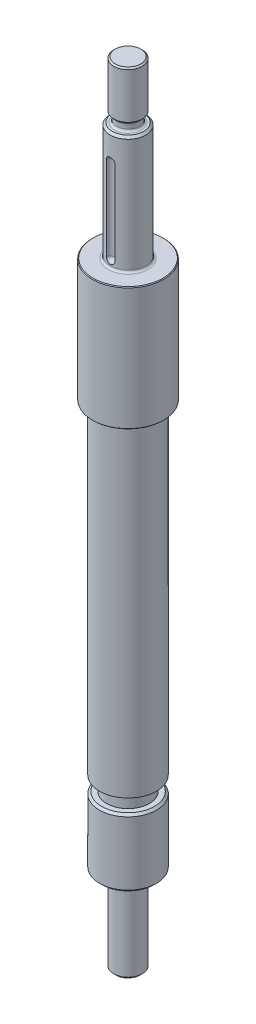
SolidWorks part; units mm, degrees
ref_plane "Front Plane" through (0, 0, 0) normal (0, 0, 1) x (1, 0, 0)
ref_plane "Top Plane" through (0, 0, 0) normal (0, 1, 0) x (1, 0, 0)
ref_plane "Right Plane" through (0, 0, 0) normal (1, 0, 0) x (0, 0, -1)
sketch "Sketch1" plane through (0, 0, 0) normal (0, 0, 1) x (1, 0, 0)
  line L0 (0, 0) -> (0, 119.1505) construction
  line L1 (0, 0) -> (2, 0)
  line L2 (2, 0) -> (2, 12)
  line L3 (2, 12) -> (4, 12)
  line L4 (4, 12) -> (4, 21.5)
  line L5 (4, 69) -> (5, 69)
  line L7 (5, 86.3) -> (2.5, 86.3)
  line L8 (2.5, 86.3) -> (2.5, 102.8)
  line L9 (2, 110.8) -> (0, 110.8)
  line L10 (2, 110.8) -> (2, 104)
  line L11 (1.6, 102.8) -> (2.5, 102.8)
  line L12 (0, 110.8) -> (0, 0)
  line L13 (5, 86.3) -> (5, 69)
  line L15 (2, 104) -> (1.6, 104)
  line L16 (1.6, 104) -> (1.6, 102.8)
  line L17 (4, 23.5) -> (4, 69)
  line L18 (4, 21.5) -> (3, 21.5)
  line L20 (4, 23.5) -> (3, 23.5)
  line L21 (3, 21.5) -> (3, 23.5)
  line L22 (0, 0) -> (0, -13.7807) construction
  point P20 (0, 119.1505)
  point P22 (0, -13.7807)
  dimension "D1" = 17.3
  dimension "D2" = 8
  dimension "D3" = 5
  dimension "D4" = 4
  dimension "D5" = 3.2
  dimension "D6" = 16.5
  dimension "D7" = 10
  dimension "D8" = 1.2
  dimension "D9" = 8
  dimension "D10" = 45.5
  dimension "D11" = 12
  dimension "D12" = 6
  dimension "D13" = 2
  dimension "D14" = 11.5
revolve "Revolve1" add sketch "Sketch1" angle 360 about L0
ref_plane "Plane2" through (0, 86.8, 0) normal (0, 1, 0) x (1, 0, 0)
sketch "Sketch2" plane through (0, 86.8, 0) normal (0, 1, 0) x (1, 0, 0)
  line L0 (0, 0) -> (6.8447, 0) construction
  circle A0 centre (0, 2.5) radius 0.6
  circle A1 centre (0, 0) radius 2.5 construction
  circle A2 centre (0, 0) radius 2.5 construction
  circle A3 centre (0, -2.5) radius 0.6
  point P11 (0.8677, 2.3446)
  dimension "D1" = 1.2
extrude "Cut-Extrude1" cut sketch "Sketch2" along normal offset from surface (13 mm away) 3 up to face at (0, 102.8, -1.6)
fillet "Fillet1" radius 0.6 4 edges at (0, 99.8, -1.9) (0, 86.8, -1.9) (0, 86.8, 1.9) (0, 99.8, 1.9)
chamfer "Chamfer1" distance 0.1 angle 45 2 edges at (0, 69, -5) (0, 86.3, -5)
chamfer "Chamfer2" distance 0.3 angle 45 2 edges at (0, 21.5, -4) (0, 12, -4)
chamfer "Chamfer3" distance 0.3 angle 45 1 edges at (0, 0, -2)
chamfer "Chamfer4" distance 0.3 angle 45 1 edges at (0, 102.8, -2.5)
chamfer "Chamfer5" distance 0.2 angle 45 2 edges at (0, 104, -2) (0, 110.8, -2)
fillet "Fillet2" radius 0.3 6 edges at (0, 23.5, -3) (0, 12, -2) (0, 69, -4) (0, 86.3, -2.5) (0, 104, -1.6) (0, 102.8, -1.6)
